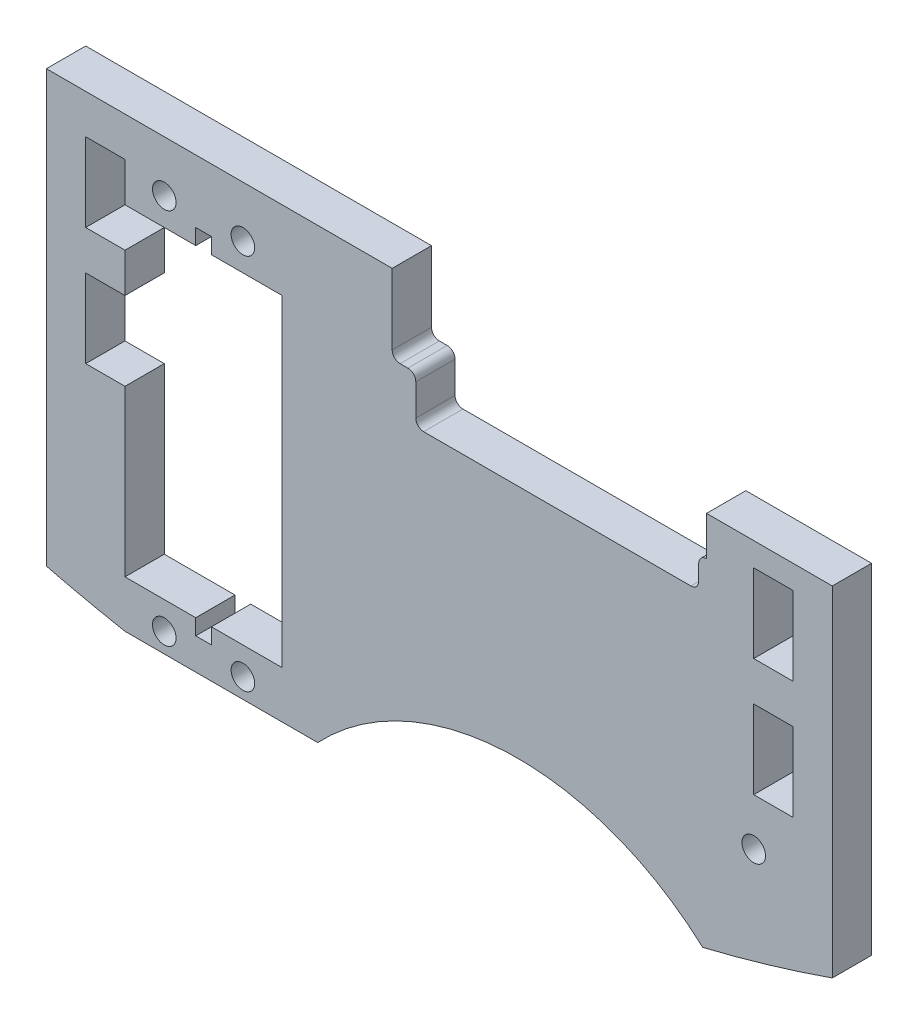
SolidWorks part; units mm, degrees
ref_plane "Plan de face" through (0, 0, 0) normal (0, 0, 1) x (1, 0, 0)
ref_plane "Plan de dessus" through (0, 0, 0) normal (0, 1, 0) x (1, 0, 0)
ref_plane "Plan de droite" through (0, 0, 0) normal (1, 0, 0) x (0, 0, -1)
sketch "Esquisse1" plane through (0, 0, 0) normal (0, 0, 1) x (1, 0, 0)
  line L0 (20, 67) -> (20, -4) construction
  line L1 (0, 0) -> (34.5245, 0)
  line L2 (0, 0) -> (0, 57)
  line L3 (0, 57) -> (44, 57)
  line L4 (100, 0) -> (100, 50)
  line L5 (10, 26.5) -> (30, 26.5) construction
  line L6 (10, 47) -> (19, 47)
  line L7 (10, 42) -> (10, 37)
  line L8 (10, 6) -> (19, 6)
  line L9 (30, 47) -> (30, 6)
  line L10 (20, 16) -> (90, 16) construction
  line L11 (85.4755, 0) -> (100, 0)
  line L12 (21, 4) -> (21, 6)
  line L13 (19, 49) -> (21, 49)
  line L14 (19, 49) -> (19, 47)
  line L15 (21, 6) -> (30, 6)
  line L16 (21, 49) -> (21, 47)
  line L17 (19, 4) -> (21, 4)
  line L18 (19, 4) -> (19, 6)
  line L19 (21, 47) -> (30, 47)
  line L20 (10, 27) -> (10, 6)
  line L21 (90, 47) -> (95, 47)
  line L22 (90, 47) -> (90, 37)
  line L23 (90, 37) -> (95, 37)
  line L24 (95, 47) -> (95, 37)
  line L25 (90, 32) -> (95, 32)
  line L26 (90, 32) -> (90, 22)
  line L27 (90, 22) -> (95, 22)
  line L28 (95, 32) -> (95, 22)
  line L29 (5, 52) -> (10, 52)
  line L30 (5, 52) -> (5, 42)
  line L31 (5, 42) -> (10, 42)
  line L32 (10, 52) -> (10, 47)
  line L33 (5, 37) -> (10, 37)
  line L34 (5, 37) -> (5, 27)
  line L35 (5, 27) -> (10, 27)
  line L36 (84, 50) -> (100, 50)
  line L37 (47, 47) -> (44, 47)
  line L38 (84, 50) -> (84, 45)
  line L39 (84, 45) -> (83, 45)
  line L40 (44, 57) -> (44, 47)
  line L42 (83, 45) -> (83, 41)
  line L43 (83, 41) -> (47, 41)
  line L44 (47, 47) -> (47, 41)
  circle A0 centre (15, 2.5) radius 1.5
  circle A1 centre (25, 2.5) radius 1.5
  circle A2 centre (25, 50.5) radius 1.5
  circle A3 centre (15, 50.5) radius 1.5
  circle A4 centre (20, 16) radius 1.5 construction
  circle A5 centre (20, 16) radius 1.5 construction
  circle A6 centre (90, 16) radius 1.5
  circle A7 centre (60, -24) radius 35 construction
  arc A8 (34.5245, 0) -> (85.4755, 0) centre (60, -24) cw
  dimension "D6" = 3.5
  dimension "D8" = 3
  dimension "D9" = 3
  dimension "D10" = 70
  dimension "D13" = 70
  dimension "D16" = 2
  dimension "D1" = 6
  dimension "D2" = 41
  dimension "D3" = 20
  dimension "D4" = 10
  dimension "D5" = 100
  dimension "D7" = 5
  dimension "D11" = 10
  dimension "D12" = 10
  dimension "D14" = 40
  dimension "D15" = 40
  dimension "D17" = 2
  dimension "D18" = 5
  dimension "D19" = 5
  dimension "D20" = 10
  dimension "D21" = 3
  dimension "D22" = 5
  dimension "D23" = 5
  dimension "D24" = 10
  dimension "D25" = 6
  dimension "D26" = 10
  dimension "D27" = 40
  dimension "D28" = 1
  dimension "D29" = 36
  dimension "D30" = 5
  dimension "D31" = 5
  dimension "D32" = 4
  dimension "D33" = 5
  dimension "D34" = 50
extrude "Boss.-Extru.1" add sketch "Esquisse1" along normal blind 5
fillet "Congé1" radius 1 5 edges at (83, 45, 2.5) (83, 41, 2.5) (47, 41, 2.5) (47, 47, 2.5) (44, 47, 2.5)
sketch "Esquisse2" plane through (0, 0, 5) normal (0, 0, 1) x (1, 0, 0)
  line L0 (0, 0) -> (34.5245, 0) construction
  line L1 (10, 27) -> (10, 6) construction
  line L2 (-40.4936, 0.9705) -> (-34.879, 14.9208)
  line L3 (159.5405, 42.1102) -> (167.1741, 28.8302)
  arc A0 (-34.879, 14.9208) -> (159.5405, 42.1102) centre (42.2645, 172) ccw
  arc A1 (-40.4936, 0.9705) -> (167.1741, 28.8302) centre (42.2645, 172) ccw
  point P3 (10, 0)
  dimension "D1" = 175
  dimension "D2" = 15
  dimension "D3" = 172
extrude "Enlèv. mat.-Extru.1" cut sketch "Esquisse2" against normal blind 10
